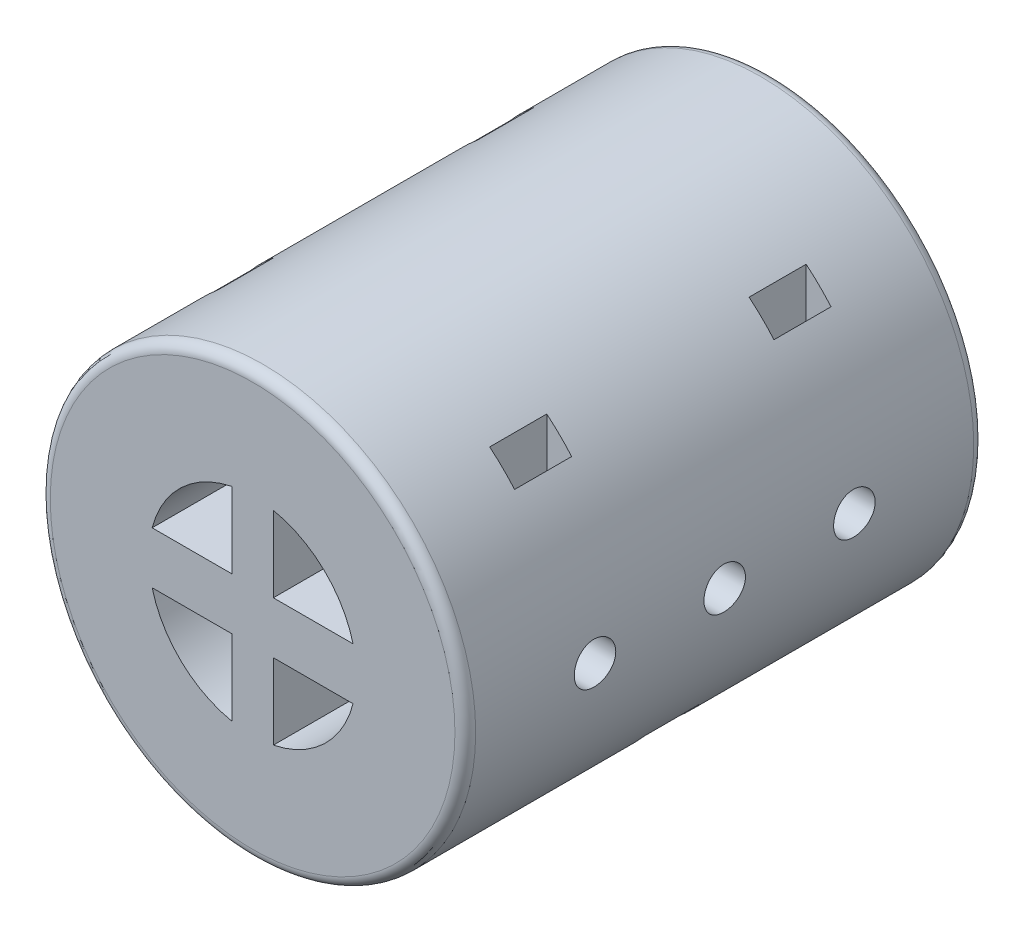
SolidWorks part; units mm, degrees
material "ABS"
ref_plane "Спереди" through (0, 0, 0) normal (0, 0, 1) x (1, 0, 0)
ref_plane "Сверху" through (0, 0, 0) normal (0, 1, 0) x (1, 0, 0)
ref_plane "Справа" through (0, 0, 0) normal (1, 0, 0) x (0, 0, -1)
other "Configuration Table"
sketch "Эскиз1" plane through (0, 0, 0) normal (0, 0, 1) x (1, 0, 0)
  circle A0 centre (0, 0) radius 20.5
  dimension "D1" = 41
extrude "Бобышка-Вытянуть1" add sketch "Эскиз1" along normal blind 50
fillet "Скругление1" radius 1 1 edges at (20.5, 0, 50)
fillet "Скругление2" radius 1 1 edges at (20.5, 0, 0)
ref_plane "Плоскость1" through (20.5, 0, 0) normal (1, 0, 0) x (0, 0, -1)
sketch "Эскиз2" plane through (20.5, 0, 0) normal (1, 0, 0) x (0, 0, -1)
  line L0 (-50, 19.5) -> (-50, -19.5) construction
  line L1 (-49, -20.5) -> (-1, -20.5) construction
  circle A0 centre (-37.5, 0) radius 2
  circle A1 centre (-25, 0) radius 2
  circle A2 centre (-12.5, 0) radius 2
  dimension "D1" = 4
  dimension "D2" = 4
  dimension "D3" = 4
  dimension "D4" = 12.5
  dimension "D5" = 12.5
  dimension "D6" = 12.5
  dimension "D7" = 20.5
  dimension "D8" = 20.5
  dimension "D9" = 20.5
extrude "Вырез-Вытянуть1" cut sketch "Эскиз2" against normal through all
sketch "Эскиз3" plane through (20.5, 0, 0) normal (1, 0, 0) x (0, 0, -1)
  line L0 (-50, 19.5) -> (-50, -19.5) construction
  line L8 (-25, 3.1754) -> (-27.75, 1.5877)
  line L9 (-37.5, 3.1754) -> (-40.25, 1.5877)
  line L10 (-40.25, 1.5877) -> (-40.25, -1.5877)
  line L11 (-40.25, -1.5877) -> (-37.5, -3.1754)
  line L12 (-37.5, -3.1754) -> (-34.75, -1.5877)
  line L13 (-34.75, -1.5877) -> (-34.75, 1.5877)
  line L14 (-34.75, 1.5877) -> (-37.5, 3.1754)
  line L15 (-27.75, 1.5877) -> (-27.75, -1.5877)
  line L16 (-27.75, -1.5877) -> (-25, -3.1754)
  line L17 (-25, -3.1754) -> (-22.25, -1.5877)
  line L18 (-22.25, -1.5877) -> (-22.25, 1.5877)
  line L19 (-22.25, 1.5877) -> (-25, 3.1754)
  line L20 (-12.5, 3.1754) -> (-15.25, 1.5877)
  line L21 (-15.25, 1.5877) -> (-15.25, -1.5877)
  line L22 (-15.25, -1.5877) -> (-12.5, -3.1754)
  line L23 (-12.5, -3.1754) -> (-9.75, -1.5877)
  line L24 (-9.75, -1.5877) -> (-9.75, 1.5877)
  line L25 (-9.75, 1.5877) -> (-12.5, 3.1754)
  circle A0 centre (-37.5, 0) radius 2.75 construction
  circle A1 centre (-25, 0) radius 2.75 construction
  circle A2 centre (-12.5, 0) radius 2.75 construction
  dimension "D4" = 5.5
  dimension "D5" = 5.5
  dimension "D6" = 5.5
  dimension "D7" = 12.5
  dimension "D8" = 12.5
  dimension "D9" = 12.5
extrude "Вырез-Вытянуть2" cut sketch "Эскиз3" against normal blind 2.4 from offset 5 offset against normal yes
mirror "Зеркальное отражение1" about plane through (0, 0, 0) normal (1, 0, 0) of "Вырез-Вытянуть2"
sketch "Эскиз4" plane through (0, 0, 50) normal (0, 0, 1) x (1, 0, 0)
  line L0 (0, 0) -> (-10, 0) construction
  line L1 (0, 0) -> (10, 0) construction
  line L2 (0, 0) -> (0, 10) construction
  line L3 (0, 0) -> (0, -10) construction
  line L4 (2, 2.5) -> (2, 9.798)
  line L5 (-2, 2.5) -> (-2, 9.798)
  line L6 (-2, -2.5) -> (-2, -9.798)
  line L7 (2, -2.5) -> (2, -9.798)
  line L8 (-9.6825, 2.5) -> (-2, 2.5)
  line L9 (-9.6825, -2.5) -> (-2, -2.5)
  line L10 (2, 2.5) -> (9.6825, 2.5)
  line L11 (2, -2.5) -> (9.6825, -2.5)
  circle A0 centre (0, 0) radius 10
  dimension "D1" = 20
  dimension "D3" = 2.5
  dimension "D4" = 2.5
  dimension "D2" = 2
  dimension "D5" = 2
  dimension "D6" = 2
  dimension "D7" = 2
extrude "Вырез-Вытянуть9" cut sketch "Эскиз4" against normal through all contours L5 A0 L8 | L10 A0 L4 | L7 A0 L11 | L9 A0 L6 region at (5.0374, 5.3975, 50) region at (-5.0374, 5.3975, 50) region at (5.0374, -5.3975, 50) region at (-5.0374, -5.3975, 50)
ref_plane "Плоскость2" through (0, 20.5, 0) normal (0, 1, 0) x (1, 0, 0)
sketch "Эскиз6" plane through (0, 20.5, 0) normal (0, 1, 0) x (1, 0, 0)
  line L1 (13.1, -34.75) -> (15.5, -34.75)
  line L2 (13.1, -34.75) -> (13.1, -40.25)
  line L3 (13.1, -40.25) -> (15.5, -40.25)
  line L4 (15.5, -34.75) -> (15.5, -40.25)
  line L5 (13.1, -34.75) -> (15.5, -40.25) construction
  line L6 (13.1, -40.25) -> (15.5, -34.75) construction
  line L8 (20.5, -49) -> (20.5, -39.4999) construction
  line L9 (-19.5, -50) -> (19.5, -50) construction
  line L16 (13.1, -22.25) -> (15.5, -22.25)
  line L17 (15.5, -22.25) -> (15.5, -27.75)
  line L18 (13.1, -22.25) -> (13.1, -27.75)
  line L19 (13.1, -27.75) -> (15.5, -27.75)
  line L20 (13.1, -9.75) -> (15.5, -9.75)
  line L21 (15.5, -9.75) -> (15.5, -15.25)
  line L22 (13.1, -9.75) -> (13.1, -15.25)
  line L23 (13.1, -15.25) -> (15.5, -15.25)
  line L24 (13.1, -34.75) -> (13.1, -22.25) construction
  point P0 (14.3, -37.5)
  dimension "D1" = 2.4
  dimension "D2" = 5.5
  dimension "D3" = 5
  dimension "D4" = 9.75
  dimension "D6" = 12.5
  dimension "D5" = 3
extrude "Вырез-Вытянуть10" cut sketch "Эскиз6" against normal blind 20.5 contours L4 L3 L2 L1 | L21 L23 L22 L20
extrude "Вырез-Вытянуть11" cut sketch "Эскиз6<5>" against normal blind 20.5 from offset 20.5 contours L17 L19 L18 L16 offset against normal yes
sketch "Эскиз6<5>" plane through (0, 20.5, 0) normal (0, 1, 0) x (1, 0, 0) same geometry as "Эскиз6"
mirror "Зеркальное отражение2" about plane through (0, 0, 0) normal (1, 0, 0) of "Вырез-Вытянуть10", "Вырез-Вытянуть11"
equation "\"D4@Эскиз4\"=\"D3@Эскиз4\""
equation "\"D5@Эскиз4\"=\"D2@Эскиз4\""
equation "\"D6@Эскиз4\"=\"D2@Эскиз4\""
equation "\"D7@Эскиз4\"=\"D2@Эскиз4\""
